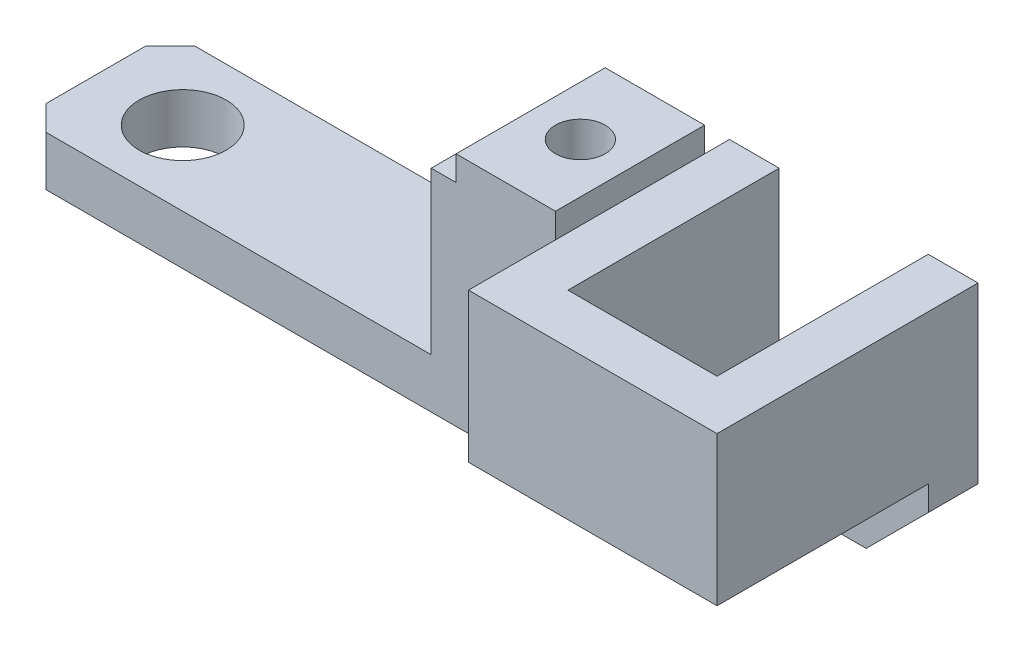
SolidWorks part; units mm, degrees
material "Plain Carbon Steel"
ref_plane "Front Plane" through (0, 0, 0) normal (0, 0, 1) x (1, 0, 0)
ref_plane "Top Plane" through (0, 0, 0) normal (0, 1, 0) x (1, 0, 0)
ref_plane "Right Plane" through (0, 0, 0) normal (1, 0, 0) x (0, 0, -1)
sketch "Sketch1" plane through (0, 0, 0) normal (0, 1, 0) x (1, 0, 0)
  line L0 (20.5, 6) -> (20.5, -6)
  line L1 (-22.5, -6) -> (22.5, -6)
  line L2 (-22.5, -6) -> (-22.5, 6)
  line L3 (-22.5, 6) -> (22.5, 6)
  line L4 (22.5, -6) -> (22.5, 6)
  line L5 (-22.5, -6) -> (22.5, 6) construction
  line L6 (-22.5, 6) -> (22.5, -6) construction
  line L7 (22.5, 6) -> (42.5, 6)
  line L8 (22.5, 6) -> (22.5, 2)
  line L9 (22.5, 2) -> (42.5, 2)
  line L10 (42.5, 6) -> (42.5, 2)
  line L11 (12.5, 6) -> (12.5, -6)
  line L12 (10.5, 6) -> (10.5, -6)
  circle A0 centre (-15.5, 0) radius 3.5
  circle A1 centre (16.5, 0) radius 2
  point P0 (0, 0)
  dimension "D4" = 7
  dimension "D7" = 4
  dimension "D1" = 7
  dimension "D2" = 12
  dimension "D3" = 45
  dimension "D5" = 33
  dimension "D6" = 35
  dimension "D8" = 4
  dimension "D9" = 6
  dimension "D10" = 4
  dimension "D11" = 20
  dimension "D12" = 43
extrude "Boss-Extrude1" add sketch "Sketch1" along normal blind 4 contours L12 L3 L2 L1 A0 region at (-4.9774, 0, 0)
extrude "Boss-Extrude2" add sketch "Sketch1<4>" along normal blind 17 contours L3 L12 L1 L11 | L1 L4 L3 L0 region at (21.5, 0, 0) region at (11.5, 0, 0)
sketch "Sketch1<4>" plane through (0, 0, 0) normal (0, 1, 0) x (1, 0, 0) same geometry as "Sketch1"
extrude "Boss-Extrude3" add sketch "Sketch1<5>" along normal blind 19 contours L3 L11 L1 L0 A1 region at (20.3558, 0, 0)
sketch "Sketch1<5>" plane through (0, 0, 0) normal (0, 1, 0) x (1, 0, 0) same geometry as "Sketch1"
extrude "Boss-Extrude4" add sketch "Sketch1<6>" along normal blind 7 contours L10 L7 L4 L9 region at (32.5, 0, -4)
sketch "Sketch1<6>" plane through (0, 0, 0) normal (0, 1, 0) x (1, 0, 0) same geometry as "Sketch1"
sketch "Sketch2" plane through (0, 7, 0) normal (0, 1, 0) x (1, 0, 0)
  line L0 (42.5, 6) -> (42.5, 2) construction
  line L1 (22.5, 6) -> (26.5, 6)
  line L2 (22.5, 6) -> (22.5, -15)
  line L3 (22.5, -15) -> (42.5, -15)
  line L4 (42.5, 6) -> (42.5, -15)
  line L5 (38.5, 2) -> (38.5, -11)
  line L6 (26.5, -11) -> (38.5, -11)
  line L7 (26.5, 2) -> (26.5, -11)
  line L9 (26.5, 6) -> (26.5, 2)
  line L10 (38.5, 6) -> (38.5, 2)
  line L11 (38.5, 6) -> (42.5, 6)
  line L13 (22.5, 6) -> (42.5, 6) construction
  line L14 (26.5, 2) -> (38.5, 2) construction
  dimension "D1" = 21
  dimension "D2" = 4
extrude "Boss-Extrude5" add sketch "Sketch2" along normal up to surface (12 mm away) up to face at (16.5, 19, 2)
chamfer "Chamfer1" distance 2 angle 45 2 edges at (-22.5, 2, 6) (-22.5, 2, -6)
sketch "Sketch3" plane through (0, 0, -2) normal (0, 0, 1) x (1, 0, 0)
  line L0 (42.5, 5) -> (37.5, 0)
  line L1 (42.5, 7) -> (42.5, 0) construction
  line L2 (22.5, 0) -> (42.5, 0) construction
  line L3 (37.5, 0) -> (42.5, 0)
  line L4 (42.5, 0) -> (42.5, 5)
  circle A0 centre (32.5, 4) radius 1.5
  line M4 (22.5, 0) -> (42.5, 0)
  line M5 (42.5, 0) -> (42.5, 7)
  dimension "D3" = 3
  dimension "D1" = 45
  dimension "D2" = 5
  dimension "D4" = 4
  dimension "D5" = 10
extrude "Cut-Extrude1" cut sketch "Sketch3" against normal through all contours A0 | L0 M5 M4 region at (40.8333, 1.6667, -2) region at (32.5, 4, -2)
